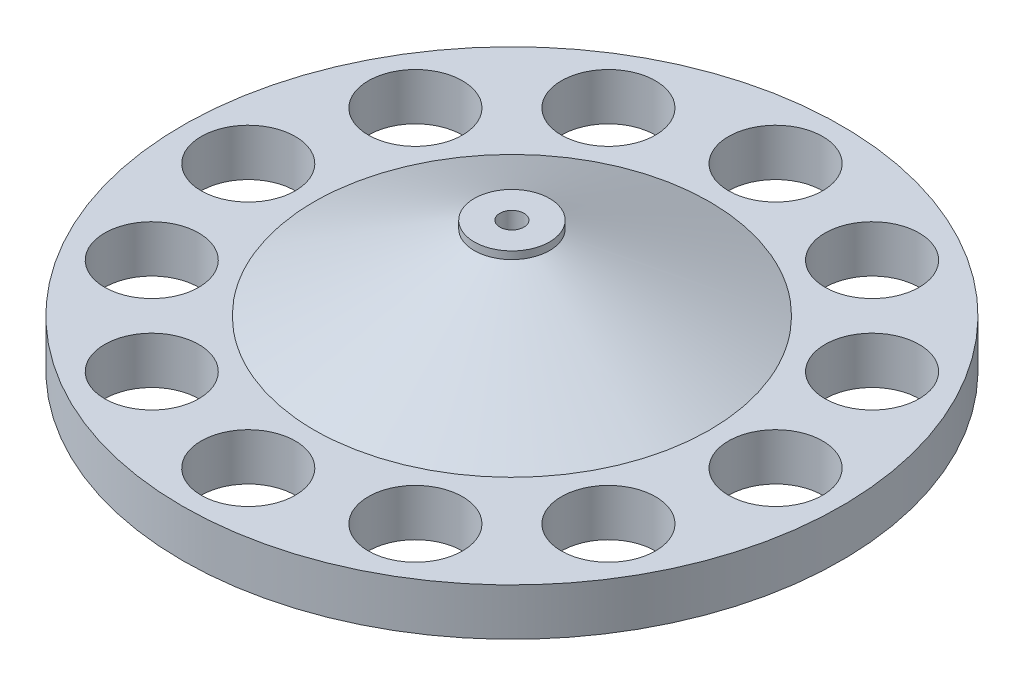
SolidWorks part; units mm, degrees
ref_plane "Front Plane" through (0, 0, 0) normal (0, 0, 1) x (1, 0, 0)
ref_plane "Top Plane" through (0, 0, 0) normal (0, 1, 0) x (1, 0, 0)
ref_plane "Right Plane" through (0, 0, 0) normal (1, 0, 0) x (0, 0, -1)
sketch "Sketch3" plane through (0, 0, 0) normal (0, 1, 0) x (1, 0, 0)
  circle A0 centre (0, 0) radius 175
  circle A11 centre (0, 140) radius 25
  circle A12 centre (70, 121.2436) radius 25
  circle A13 centre (121.2436, 70) radius 25
  circle A14 centre (140, 0) radius 25
  circle A15 centre (121.2436, -70) radius 25
  circle A16 centre (70, -121.2436) radius 25
  circle A17 centre (0, -140) radius 25
  circle A18 centre (-70, -121.2436) radius 25
  circle A19 centre (-121.2436, -70) radius 25
  circle A20 centre (-140, 0) radius 25
  circle A21 centre (-121.2436, 70) radius 25
  circle A22 centre (-70, 121.2436) radius 25
  dimension "D1" = 12
extrude "Boss-Extrude1" add sketch "Sketch3" along normal blind 25
sketch "Sketch4" plane through (0, 25, 0) normal (0, 1, 0) x (1, 0, 0)
  circle A0 centre (0, 0) radius 105
ref_plane "Plane1" through (0, 65, 0) normal (0, 1, 0) x (1, 0, 0)
sketch "Sketch5" plane through (0, 65, 0) normal (0, 1, 0) x (1, 0, 0)
  circle A0 centre (0, 0) radius 20
sketch "Sketch6" plane through (0, 0, 0) normal (0, -1, 0) x (1, 0, 0)
  circle A0 centre (0, 0) radius 10
extrude "Cut-Extrude1" cut sketch "Sketch6" against normal blind 25
loft "Loft2" add profiles "Sketch4", "Sketch5" connector at (74.572, 25, -73.9189) connector at (17.1376, 65, -10.3103)
sketch "Sketch7" plane through (0, 0, 0) normal (0, -1, 0) x (1, 0, 0)
  circle A0 centre (0, 0) radius 103
  dimension "D1" = 206
extrude "Cut-Extrude2" cut sketch "Sketch7" against normal blind 18
fillet "Fillet1" radius 8 1 edges at (0, 0, -103)
sketch "Sketch8" plane through (0, 65, 0) normal (0, 1, 0) x (1, 0, 0)
  circle A0 centre (0, 0) radius 20
extrude "Boss-Extrude2" add sketch "Sketch8" along normal blind 4
sketch "Sketch9" plane through (0, 69, 0) normal (0, 1, 0) x (1, 0, 0)
  circle A0 centre (0, 0) radius 6.4
  dimension "D1" = 12.8
extrude "Cut-Extrude3" cut sketch "Sketch9" against normal through all
